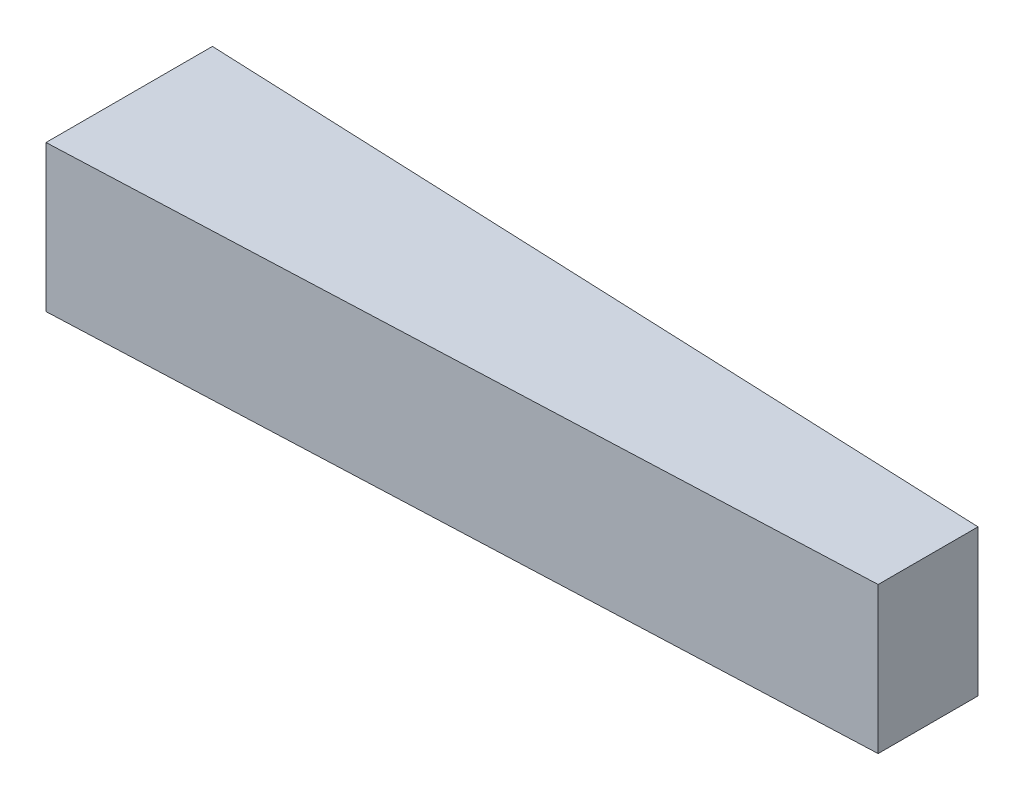
SolidWorks part; units mm, degrees
material "6061 합금"
ref_plane "정면" through (0, 0, 0) normal (0, 0, 1) x (1, 0, 0)
ref_plane "윗면" through (0, 0, 0) normal (0, 1, 0) x (1, 0, 0)
ref_plane "우측면" through (0, 0, 0) normal (1, 0, 0) x (0, 0, -1)
sketch "스케치1" plane through (0, 0, 0) normal (0, 1, 0) x (1, 0, 0)
  line L0 (0, 25) -> (0, -25)
  line L1 (240, 15) -> (240, -15)
  line L2 (240, -15) -> (0, -25)
  line L3 (0, 25) -> (240, 15)
  line L4 (10, 14.5747) -> (230, 5.408)
  line L5 (230, 5.408) -> (230, -5.408)
  line L6 (230, -5.408) -> (10, -14.5747)
  line L7 (10, 14.5747) -> (10, -14.5747)
  line L8 (-52, 0) -> (298, 0) construction
  point P3 (0, 0)
  point P10 (240, 0)
  dimension "D1" = 50
  dimension "D2" = 30
  dimension "D3" = 240
  dimension "D5" = 58
  dimension "D6" = 52
  dimension "D4" = 10
extrude "보스-돌출1" add sketch "스케치1" along normal mid plane 44
extrude "보스-돌출2" add sketch "스케치1<2>" along normal blind 10 from surface contours L4 L7 L6 L5 | L4 L5 L6 L7 region at (103.1798, 0, 0) starting at face at (120, -22, 0)
sketch "스케치1<2>" plane through (0, 0, 0) normal (0, 1, 0) x (1, 0, 0) same geometry as "스케치1"
extrude "보스-돌출3" add sketch "스케치1<3>" against normal blind 10 from surface contours L4 L7 L6 L5 | L8 L7 L6 L5 region at (103.1798, 0, 5.3461) region at (103.1798, 0, -5.3461) starting at face at (120, 22, 0)
sketch "스케치1<3>" plane through (0, 0, 0) normal (0, 1, 0) x (1, 0, 0) same geometry as "스케치1"
